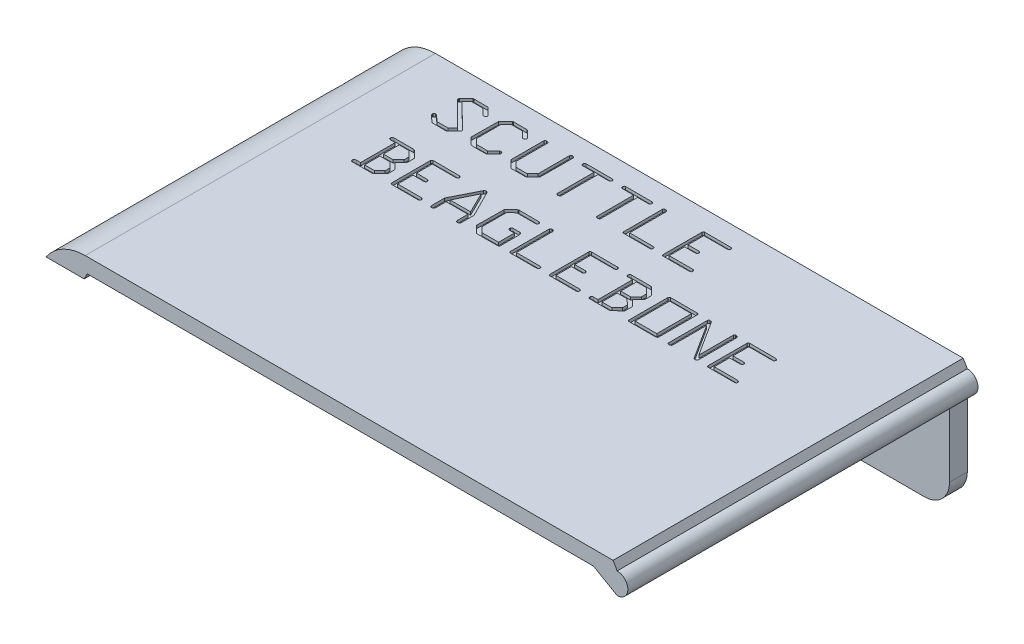
SolidWorks part; units mm, degrees
ref_plane "Front Plane" through (0, 0, 0) normal (0, 0, 1) x (1, 0, 0)
ref_plane "Top Plane" through (0, 0, 0) normal (0, 1, 0) x (1, 0, 0)
ref_plane "Right Plane" through (0, 0, 0) normal (1, 0, 0) x (0, 0, -1)
sketch "Sketch1" plane through (0, 0, 0) normal (0, 0, 1) x (1, 0, 0)
  line L1 (0, 0) -> (105.0595, 0)
  line L2 (0, 0) -> (8.3161, 16.1605)
  line L3 (15.4295, 20.5) -> (105.0595, 20.5)
  line L4 (105.0595, 0) -> (105.0595, 20.5)
  arc A0 (8.3161, 16.1605) -> (15.4295, 20.5) centre (15.4295, 12.5) cw
  point P7 (10.5491, 20.5)
  dimension "D3" = 8
  dimension "D1" = 89.63
  dimension "D2" = 20.5
  dimension "D4" = 62.77
extrude "Boss-Extrude1" add sketch "Sketch1" along normal blind 3
sketch "Sketch2" plane through (0, 0, 0) normal (0, 0, 1) x (1, 0, 0)
  line L1 (8.3161, 16.1605) -> (0, 0)
  line L2 (105.0595, 20.5) -> (15.4295, 20.5)
  line L3 (15.4295, 18) -> (105.0595, 18)
  line L4 (105.0595, 20.5) -> (105.0595, 18)
  line L5 (105.0595, 0) -> (105.0595, 20.5) construction
  line L8 (10.539, 15.0166) -> (2.8116, 0)
  line L9 (0, 0) -> (105.0595, 0) construction
  line L10 (2.8116, 0) -> (0, 0)
  arc A2 (15.4295, 20.5) -> (8.3161, 16.1605) centre (15.4295, 12.5) ccw construction
  arc A4 (15.4295, 18) -> (10.539, 15.0166) centre (15.4295, 12.5) ccw
  arc A5 (15.4295, 20.5) -> (8.3161, 16.1605) centre (15.4295, 12.5) ccw
  dimension "D1" = 2.5
  dimension "D2" = 2.5
extrude "Boss-Extrude2" add sketch "Sketch2" along normal blind 59
fillet "Fillet1" radius 4.25 1 edges at (105.0595, 0, 1.5)
sketch "Sketch3" plane through (0, 0, 0) normal (0, 0, -1) x (-1, 0, 0)
  line L0 (-8.3161, 16.1605) -> (0, 0) construction
  line L1 (0, 0) -> (-8.5584, 0)
  line L2 (0, 0) -> (0, 4)
  line L3 (0, 4) -> (-8.5584, 4)
  line L4 (-8.5584, 0) -> (-8.5584, 4)
  point P5 (-2.0584, 4)
  dimension "D1" = 4
  dimension "D2" = 6.5
extrude "Cut-Extrude1" cut sketch "Sketch3" against normal through all
sketch "Sketch4" plane through (0, 0, 0) normal (0, 0, -1) x (-1, 0, 0)
  line L0 (-105.0595, 4.25) -> (-105.0595, 20.5) construction
  line L1 (-105.0595, 20.5) -> (-15.4295, 20.5) construction
  line L2 (-105.0595, 19.3) -> (-105.0595, 15.7)
  arc A0 (-105.0595, 19.3) -> (-105.0595, 15.7) centre (-105.0595, 17.5) ccw
  dimension "D1" = 3
  dimension "D2" = 1.8
extrude "Boss-Extrude3" add sketch "Sketch4" against normal up to surface (59 mm away) contours A0 L2 up to face at (33.2166, 14.7329, 59)
sketch "Sketch5" plane through (0, 0, 0) normal (0, 0, -1) x (-1, 0, 0)
  line L0 (-105.0595, 19.3) -> (-105.0595, 20.5)
  line L1 (-105.0595, 20.5) -> (-104.3667, 20.5)
  line L2 (-105.0595, 20.5) -> (-15.4295, 20.5) construction
  line L3 (-104.3667, 20.5) -> (-105.0595, 19.3)
  dimension "D1" = 30
extrude "Cut-Extrude2" cut sketch "Sketch5" against normal through all
fillet "Fillet2" radius 2 1 edges at (8.5584, 0, 1.5)
sketch "Sketch7" plane through (0, 0, 59) normal (0, 0, 1) x (1, 0, 0)
  line L0 (105.0595, 15.7) -> (101.0758, 18)
  line L1 (15.4295, 18) -> (105.0595, 18) construction
  line L2 (101.0758, 18) -> (105.0595, 18)
  line L3 (105.0595, 18) -> (105.0595, 15.7)
  dimension "D1" = 30
extrude "Boss-Extrude4" add sketch "Sketch7" against normal up to surface (56 mm away) up to face at (47.4548, 8.0359, 3)
sketch "Sketch12" plane through (0, 0, 3) normal (0, 0, 1) x (1, 0, 0)
  line L0 (2.0584, 4) -> (8.5584, 4)
  line L1 (8.5584, 4) -> (8.5584, 16.5973) construction
  line L2 (8.5584, 16.5973) -> (2.0584, 4)
  line L3 (8.5584, 4) -> (17.0491, 20.5)
  line L4 (104.3667, 20.5) -> (15.4295, 20.5) construction
  line L5 (15.4295, 20.5) -> (17.0491, 20.5)
  line L6 (4.87, 4) -> (10.539, 15.0166) construction
  arc A0 (15.4295, 20.5) -> (8.3161, 16.1605) centre (15.4295, 12.5) ccw construction
  arc A1 (15.4295, 20.5) -> (8.5584, 16.5973) centre (15.4295, 12.5) ccw
  dimension "D1" = 6.5
extrude "Boss-Extrude6" add sketch "Sketch12" along normal up to surface (56 mm away) up to face at (47.2975, 15.2863, 59)
sketch "Sketch8" plane through (0, 0, 0) normal (1, 0, 0) x (0, 0, -1)
  line L0 (-3, 4) -> (-3, 17)
  line L1 (0, 4) -> (-59, 4) construction
  line L2 (-3, 17) -> (-16, 17)
  line L3 (-16, 17) -> (-29, 4)
  line L4 (-29, 4) -> (-3, 4)
  line L5 (-42, 17) -> (-39.7077, 4)
  line L6 (-42, 17) -> (-59, 17)
  line L7 (-59, 4) -> (-59, 17)
  line L9 (-59, 16.1605) -> (-59, 4) construction
  line L10 (-39.7077, 4) -> (-59, 4)
  line L14 (-3, 4) -> (-3, 2) construction
  dimension "D1" = 13
  dimension "D2" = 80
  dimension "D3" = 17
  dimension "D5" = 45
  dimension "D6" = 13
extrude "Cut-Extrude4" cut sketch "Sketch8" along normal blind 16 contours L10 L6 L7 | L2 L3 L4 L0 region at (0, 10.3632, 49.9149)
sketch "Sketch9" plane through (0, 20.5, 0) normal (0, 1, 0) x (1, 0, 0)
  text T0 "SCUTTLE\r\nBEAGLEBONE" font "SWTxt" height 7
extrude "Cut-Extrude5" cut sketch "Sketch9" against normal blind 0.5
fillet "Fillet3" radius 6 1 edges at (12.0316, 17, 42)
fillet "Fillet4" radius 10 1 edges at (12.0316, 17, 16)
fillet "Fillet5" radius 4 1 edges at (12.0316, 17, 3)
sketch "Sketch13" plane through (0, 20.5, 0) normal (0, 1, 0) x (1, 0, 0)
  line L0 (2.0584, -29) -> (2.0584, -39.7077) construction
  line L1 (8.8151, -59) -> (15.4295, -59) construction
  circle A0 centre (5.5584, -35) radius 2.5
  dimension "D2" = 5
  dimension "D1" = 3.5
  dimension "D3" = 24
extrude "Cut-Extrude7" cut sketch "Sketch13" against normal blind 40
sketch "Sketch14" plane through (0, 4, 0) normal (0, -1, 0) x (1, 0, 0)
  line L1 (2.0584, 29) -> (8.5584, 29)
  line L2 (2.0584, 29) -> (2.0584, 39.7077)
  line L3 (2.0584, 39.7077) -> (8.5584, 39.7077)
  line L4 (8.5584, 29) -> (8.5584, 39.7077)
  circle A0 centre (5.5584, 35) radius 1.5
  dimension "D1" = 3
extrude "Boss-Extrude7" add sketch "Sketch14" against normal blind 2.5
sketch "Sketch15" plane through (0, 0, 39.7077) normal (0, 0, 1) x (1, 0, 0)
  line L0 (2.0584, 4) -> (3.3448, 6.5)
  line L1 (3.3448, 6.5) -> (2.0584, 6.5)
  line L2 (2.0584, 6.5) -> (2.0584, 4)
extrude "Cut-Extrude8" cut sketch "Sketch15" against normal through all
fillet "Fillet6" radius 1 1 edges at (8.0584, 15.6597, 35)
sketch "Sketch16" plane through (0, 18, 0) normal (0, -1, 0) x (1, 0, 0)
  text T0 "V1.0" font "Century Gothic" height 6
extrude "Cut-Extrude9" cut sketch "Sketch16" against normal blind 0.5
sketch "Sketch17" plane through (0, 0, 0) normal (1, 0, 0) x (0, 0, -1)
  line L0 (-4.5482, 16.1605) -> (-5.5526, 16.9396)
  line L1 (-5.5526, 16.9396) -> (-15.3597, 16.9396) construction
  line L2 (-15.3597, 16.9396) -> (-17.9873, 14.9013)
  line L3 (-17.9873, 14.9013) -> (-3.4078, 14.7597)
  arc A0 (-11.8579, 17) -> (-15.8685, 16.1605) centre (-11.8579, 7) ccw construction
  arc A1 (-5.5526, 16.9396) -> (-15.3597, 16.9396) centre (-10.4561, 10.6186) ccw
  arc A2 (-3, 13) -> (-4.5482, 16.1605) centre (-7, 13) ccw construction
  arc A3 (-15.8685, 16.1605) -> (-18.9289, 14.0711) centre (-11.8579, 7) ccw construction
  arc A4 (-3.4078, 14.7597) -> (-4.5482, 16.1605) centre (-7, 13) ccw
  dimension "D1" = 8
extrude "Cut-Extrude10" cut sketch "Sketch17" along normal blind 24 contours A1 L2 L3 A4 L0
